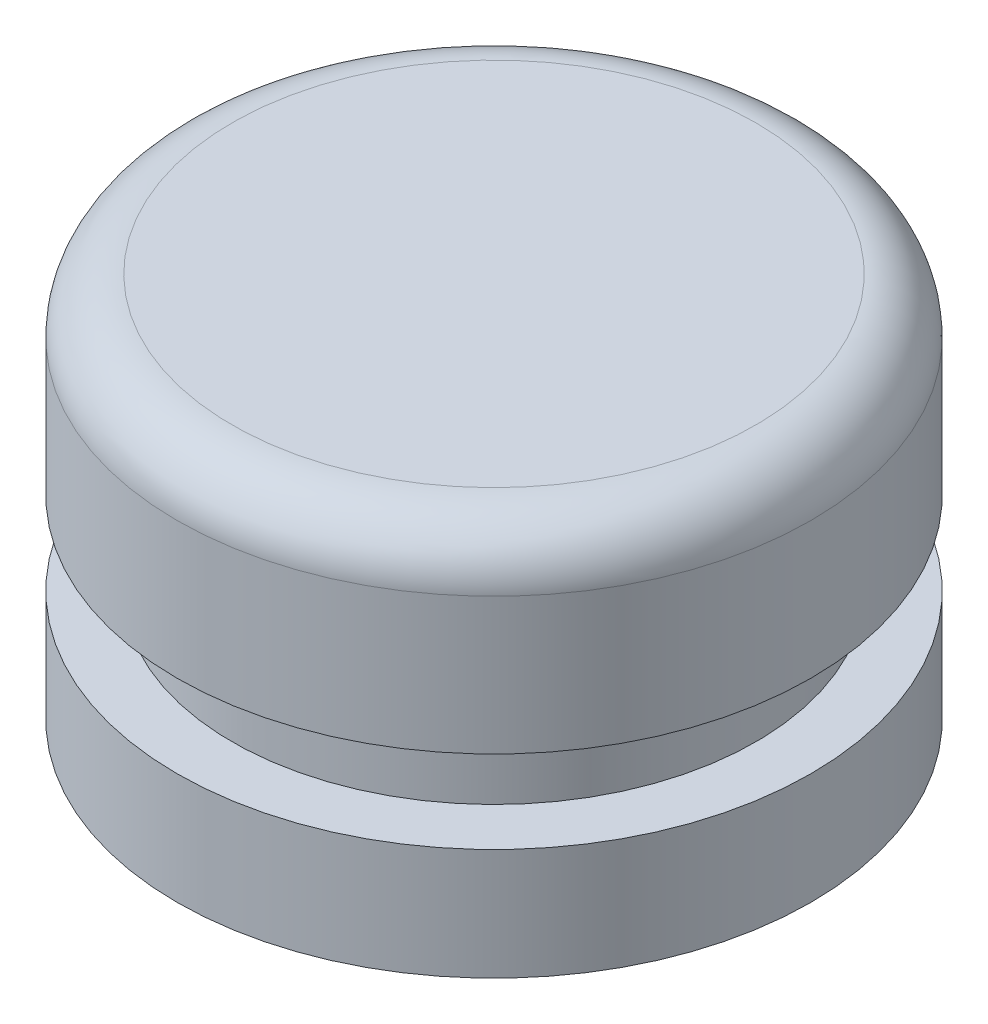
SolidWorks part; units mm, degrees
material "AISI 316 Annealed Stainless Steel Bar (SS)"
ref_plane "Front Plane" through (0, 0, 0) normal (0, 0, 1) x (1, 0, 0)
ref_plane "Top Plane" through (0, 0, 0) normal (0, 1, 0) x (1, 0, 0)
ref_plane "Right Plane" through (0, 0, 0) normal (1, 0, 0) x (0, 0, -1)
sketch "Sketch1" plane through (0, 0, 0) normal (0, 0, 1) x (1, 0, 0)
  line L0 (-0.5, 1.9563) -> (-0.5, 8.9563) construction
  line L1 (5.25, 1.9563) -> (-6.25, 1.9563) construction
  line L2 (5.25, 1.9563) -> (5.25, 8.9563) construction
  line L3 (5.25, 8.9563) -> (-6.25, 8.9563) construction
  line L4 (-6.25, 1.9563) -> (-6.25, 8.9563) construction
  line L5 (5.25, 1.9563) -> (-6.25, 8.9563) construction
  line L6 (5.25, 8.9563) -> (-6.25, 1.9563) construction
  line L7 (-0.5, 8.9563) -> (-6.25, 8.9563)
  line L8 (-6.25, 8.9563) -> (-6.25, 5.478)
  line L9 (-6.25, 5.478) -> (-5.25, 5.478)
  line L10 (-5.25, 5.478) -> (-5.25, 3.978)
  line L11 (-5.25, 3.978) -> (-6.25, 3.978)
  line L12 (-6.25, 3.978) -> (-6.25, 1.9563)
  line L13 (-0.5, 7.9563) -> (-5.25, 7.9563)
  line L14 (-5.25, 7.9563) -> (-5.25, 6.478)
  line L15 (-5.25, 6.478) -> (-4.25, 6.478)
  line L16 (-4.25, 6.478) -> (-4.25, 2.978)
  line L17 (-4.25, 2.978) -> (-5.25, 2.978)
  line L18 (-5.25, 2.978) -> (-5.25, 1.9563)
  line L19 (-0.5, 8.9563) -> (-0.5, 7.9563)
  line L20 (-5.25, 1.9563) -> (-6.25, 1.9563)
  point P0 (-0.5, 5.4563)
  dimension "D1" = 11.5
  dimension "D2" = 7
  dimension "D3" = 1.5
  dimension "D4" = 1
  dimension "D5" = 1
revolve "Revolve1" add sketch "Sketch1" angle 360 about L0
fillet "Fillet1" radius 2 1 edges at (-0.5, 2.978, -3.75)
fillet "Fillet2" radius 2 1 edges at (-0.5, 2.978, -4.75)
fillet "Fillet3" radius 2 1 edges at (-0.5, 6.478, -3.75)
fillet "Fillet4" radius 1 1 edges at (-0.5, 8.9563, -5.75)
